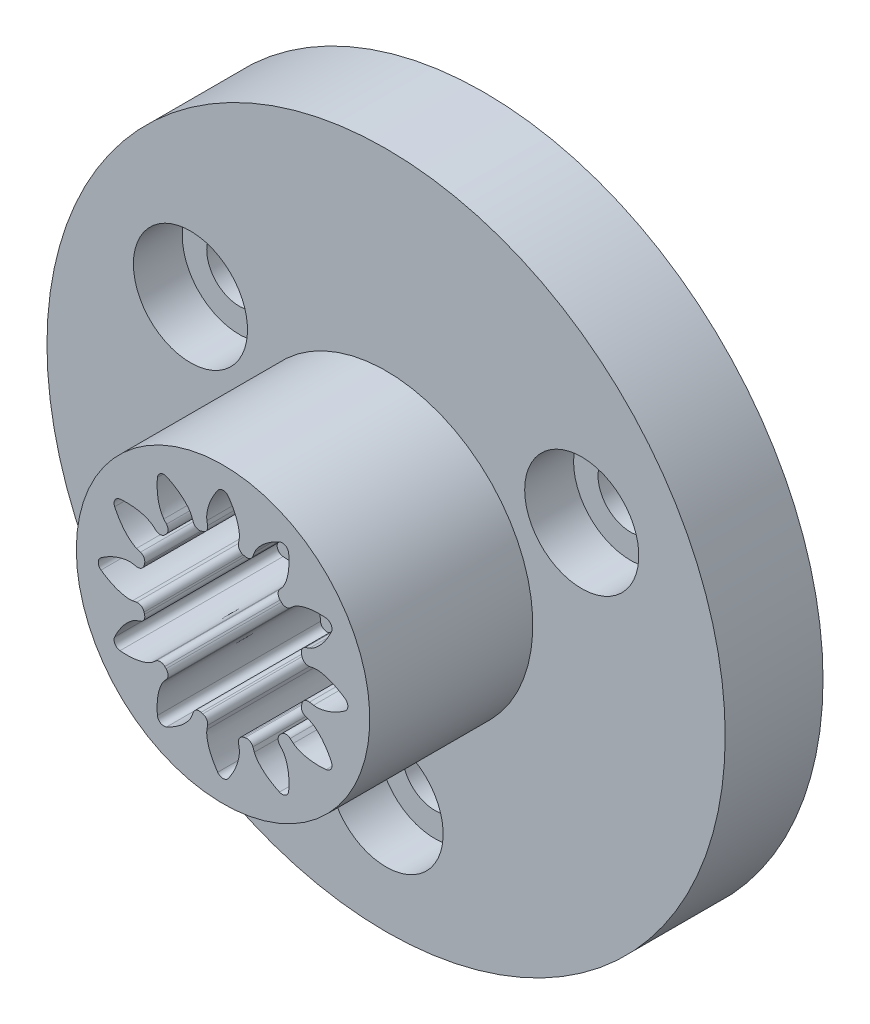
SolidWorks part; units mm, degrees
ref_plane "前视基准面" through (0, 0, 0) normal (0, 0, 1) x (1, 0, 0)
ref_plane "上视基准面" through (0, 0, 0) normal (0, 1, 0) x (1, 0, 0)
ref_plane "右视基准面" through (0, 0, 0) normal (1, 0, 0) x (0, 0, -1)
other "Configuration Table"
sketch "草图1" plane through (0, 0, 0) normal (0, 0, 1) x (1, 0, 0)
  line L0 (0, 0) -> (2.9589, 0.4951) construction
  line L1 (0, 0) -> (2.7754, 0.4945)
  line L2 (0, 0) -> (2.7754, -0.4945)
  line L3 (0, 0) -> (2.9589, -0.4951) construction
  line L4 (0, 0) -> (3.375, 0) construction
  line L5 (2.9589, 0.4951) -> (2.9589, -0.4951) construction
  circle A0 centre (0, 0) radius 2.5
  circle A1 centre (0, 0) radius 3.375
  circle A2 centre (0, 0) radius 2.8191 construction
  circle A3 centre (0, 0) radius 3 construction
  circle A4 centre (0, 0) radius 4
  spline S0 degree 4 poles (2.7754, 0.4945) (2.7965, 0.4983) (2.8563, 0.5044) (2.9715, 0.4981) (3.155, 0.4625) (3.3831, 0.3798) (3.6579, 0.2333) (3.9507, 0.0149) (4.2346, -0.2684) (4.4954, -0.613) (4.7115, -0.987) (4.8839, -1.3829) (5.0203, -1.8149) (5.1328, -2.3646) (5.1817, -3.0328) (5.1248, -3.8095) (4.9287, -4.6522) (4.6143, -5.4575) (4.193, -6.2129) (3.681, -6.9077) (3.0853, -7.5359) (2.4263, -8.0895) (1.701, -8.5684) (1.04, -8.914) (0.4266, -9.1654) (-0.0223, -9.3191) (-0.4284, -9.4348) (-0.7, -9.5016) (-1.0855, -9.5845) (-1.3803, -9.6303) (-1.6758, -9.673) (-1.8263, -9.6854) (-1.9227, -9.6957) knots 0 0 0 0 0 0.005604 0.015718 0.02996 0.048734 0.068727 0.096889 0.125051 0.153212 0.181374 0.209535 0.237696 0.271429 0.327752 0.384075 0.440398 0.496721 0.553044 0.609367 0.66569 0.722013 0.778336 0.834659 0.86282 0.890982 0.909091 0.931818 0.954545 0.977273 1 1 1 1 1 construction
  spline S1 degree 4 poles (2.7754, 0.4945) (2.7965, 0.4983) (2.8563, 0.5044) (2.9715, 0.4981) (3.155, 0.4625) (3.3831, 0.3798) (3.6579, 0.2333) (3.9507, 0.0149) (4.2346, -0.2684) (4.4954, -0.613) (4.7115, -0.987) (4.8839, -1.3829) (5.0203, -1.8149) (5.1328, -2.3646) (5.1817, -3.0328) (5.1248, -3.8095) (4.9287, -4.6522) (4.6143, -5.4575) (4.193, -6.2129) (3.681, -6.9077) (3.0853, -7.5359) (2.4263, -8.0895) (1.701, -8.5684) (1.04, -8.914) (0.4266, -9.1654) (-0.0223, -9.3191) (-0.3334, -9.4077) (-0.489, -9.4485) (-0.5501, -9.4637) knots 0 0 0 0 0 0.005604 0.015718 0.02996 0.048734 0.068727 0.096889 0.125051 0.153212 0.181374 0.209535 0.237696 0.271429 0.327752 0.384075 0.440398 0.496721 0.553044 0.609367 0.66569 0.722013 0.778336 0.834659 0.86282 0.890982 0.909091 0.909091 0.909091 0.909091 0.909091
  spline S2 degree 4 poles (2.7754, -0.4945) (2.7965, -0.4983) (2.8563, -0.5044) (2.9715, -0.4981) (3.155, -0.4625) (3.3831, -0.3798) (3.6579, -0.2333) (3.9507, -0.0149) (4.2346, 0.2684) (4.4954, 0.613) (4.7115, 0.987) (4.8839, 1.3829) (5.0203, 1.8149) (5.1328, 2.3646) (5.1817, 3.0328) (5.1248, 3.8095) (4.9287, 4.6522) (4.6143, 5.4575) (4.193, 6.2129) (3.681, 6.9077) (3.0853, 7.5359) (2.4263, 8.0895) (1.701, 8.5684) (1.04, 8.914) (0.4266, 9.1654) (-0.0223, 9.3191) (-0.4284, 9.4348) (-0.7, 9.5016) (-1.0855, 9.5845) (-1.3803, 9.6303) (-1.6758, 9.673) (-1.8263, 9.6854) (-1.9227, 9.6957) knots 0 0 0 0 0 0.005604 0.015718 0.02996 0.048734 0.068727 0.096889 0.125051 0.153212 0.181374 0.209535 0.237696 0.271429 0.327752 0.384075 0.440398 0.496721 0.553044 0.609367 0.66569 0.722013 0.778336 0.834659 0.86282 0.890982 0.909091 0.931818 0.954545 0.977273 1 1 1 1 1 construction
  spline S3 degree 4 poles (2.7754, -0.4945) (2.7965, -0.4983) (2.8563, -0.5044) (2.9715, -0.4981) (3.155, -0.4625) (3.3831, -0.3798) (3.6579, -0.2333) (3.9507, -0.0149) (4.2346, 0.2684) (4.4954, 0.613) (4.7115, 0.987) (4.8839, 1.3829) (5.0203, 1.8149) (5.1328, 2.3646) (5.1817, 3.0328) (5.1248, 3.8095) (4.9287, 4.6522) (4.6143, 5.4575) (4.193, 6.2129) (3.681, 6.9077) (3.0853, 7.5359) (2.4263, 8.0895) (1.701, 8.5684) (1.04, 8.914) (0.4266, 9.1654) (-0.0223, 9.3191) (-0.3334, 9.4077) (-0.489, 9.4485) (-0.5501, 9.4637) knots 0 0 0 0 0 0.005604 0.015718 0.02996 0.048734 0.068727 0.096889 0.125051 0.153212 0.181374 0.209535 0.237696 0.271429 0.327752 0.384075 0.440398 0.496721 0.553044 0.609367 0.66569 0.722013 0.778336 0.834659 0.86282 0.890982 0.909091 0.909091 0.909091 0.909091 0.909091
  point P16 (2.9589, 0)
  dimension "内啮合齿顶圆直径" = 5
  dimension "内啮合分度圆直径" = 6
  dimension "内啮合基圆直径" = 5.6382
  dimension "内啮合齿根圆直径" = 6.75
  dimension "外径" = 8
  dimension "渐开线镜像线夹角" = 9.5
extrude "凸台-拉伸1" add sketch "草图1" along normal blind 5 contours A4 | A0
extrude "切除-拉伸2" cut sketch "草图1<3>" along normal through all contours A0 S3 A1 S1 | A1 S3 S1 region at (2.9183, 0, 0) region at (3.5716, 0, 0)
sketch "草图1<3>" plane through (0, 0, 0) normal (0, 0, 1) x (1, 0, 0) same geometry as "草图1"
fillet "圆角1" radius 0.2 3 edges at (2.4612, -0.4385, 2.5) (2.4612, 0.4385, 2.5) (3.9496, 0, 2.5)
pattern_circular "阵列(圆周)1" count 12 over 360 about axis through (0, 0, 5) along (0, 0, 1) of "切除-拉伸2", "圆角1"
sketch "草图2" plane through (0, 0, 0) normal (0, 0, -1) x (-1, 0, 0)
  circle A0 centre (0, 0) radius 4
  circle A1 centre (0, 0) radius 4.5
  dimension "D1" = 9
  dimension "D2" = 8
extrude "凸台-拉伸3" add sketch "草图2" against normal through all
sketch "草图3" plane through (0, 0, 0) normal (0, 0, -1) x (-1, 0, 0)
  line L0 (0, 0) -> (0, -6.9282) construction
  line L1 (6, 3.4641) -> (0, 0) construction
  line L2 (-6, 3.4641) -> (0, 0) construction
  circle A0 centre (0, -6.9282) radius 1.75
  circle A1 centre (0, -6.9282) radius 1
  circle A2 centre (6, 3.4641) radius 1
  circle A3 centre (6, 3.4641) radius 1.75
  circle A4 centre (-6, 3.4641) radius 1.75
  circle A5 centre (-6, 3.4641) radius 1
  circle A6 centre (0, 0) radius 10.4
  circle A7 centre (0, 0) radius 6.9282 construction
  point P3 (-5.9466, 3.4333)
  point P11 (-6, 3.4641)
  dimension "D1" = 3.5
  dimension "D2" = 2
  dimension "D3" = 20.8
  dimension "D4" = 13.8564
  dimension "D5" = 120
  dimension "D6" = 120
extrude "凸台-拉伸4" add sketch "草图3" along normal blind 3 contours A2 | A6 | A1 | A5 region at (-6, 3.4641, 0)
extrude "切除-拉伸3" cut sketch "草图3<3>" along normal blind 1.5 contours A0 | A3 | A4
sketch "草图3<3>" plane through (0, 0, 0) normal (0, 0, -1) x (-1, 0, 0) same geometry as "草图3"
equation "\"m\"= 0.5'模数"
equation "\"z1\"= 12'外啮合齿轮数"
equation "\"a\"= 20度'压力角"
equation "\"z2\"= 12'内啮合齿轮数"
equation "\"hax\"= 0.5'齿顶高系数"
equation "\"cx\"= 0.25'顶隙系数"
equation "\"ha\"= \"hax\" * \"m\"'齿顶高"
equation "\"hf\"= ( \"hax\" + \"cx\" ) * \"m\"'齿根高"
equation "\"d1\"= \"m\" * \"z1\"'外啮合分度圆直径"
equation "\"da1\"= ( \"z1\" + 2 ) * \"m\"'外啮合齿顶圆直径"
equation "\"df1\"= \"d1\" - 2 * \"hf\"'外啮合齿根圆直径"
equation "\"db1\"= \"d1\" * cos ( \"a\" )'外啮合基圆直径"
equation "\"p\"= \"m\" * PI'齿距"
equation "\"d2\"= \"m\" * \"z2\"'内啮合分度圆直径"
equation "\"db2\"= \"d2\" * cos ( \"a\" )'内啮合基圆直径"
equation "\"da2\"= ( \"z2\" - 2 ) * \"m\"'内啮合齿顶圆直径"
equation "\"df2\"= \"d2\" + 2 * \"hf\"'内啮合齿根圆直径"
equation "\"内啮合齿顶圆直径@草图1\"= \"da2\""
equation "\"内啮合齿根圆直径@草图1\"= \"df2\""
equation "\"内啮合分度圆直径@草图1\"= \"d2\""
equation "\"内啮合基圆直径@草图1\"= \"db2\""
equation "\"渐开线镜像线夹角@草图1\"=360度 / 4 / \"z2\" + 2"
equation "\"do\"= 8'外圈直径"
equation "\"h\"= 5'厚度"
equation "\"外径@草图1\"= \"do\""
equation "\"厚度@凸台-拉伸1\"= \"h\""
equation "\"内啮合齿轮数@阵列(圆周)1\"= \"z2\""
equation "\"edo\"= 10'期望的外圈直径"
equation "\"D1@圆角1\"=0.4 *\"m\""
